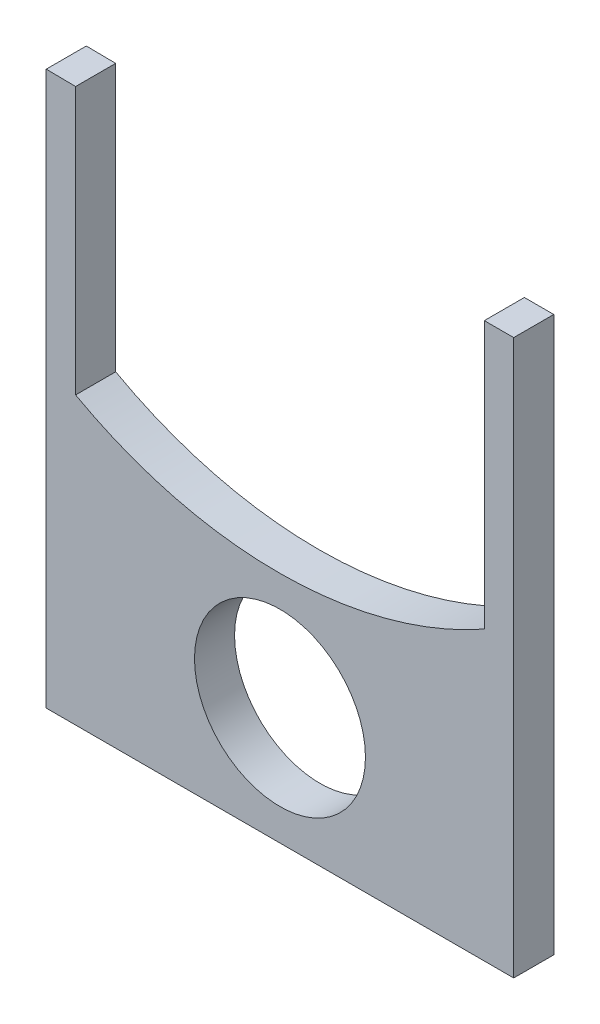
SolidWorks part; units mm, degrees
ref_plane "Front Plane" through (0, 0, 0) normal (0, 0, 1) x (1, 0, 0)
ref_plane "Top Plane" through (0, 0, 0) normal (0, 1, 0) x (1, 0, 0)
ref_plane "Right Plane" through (0, 0, 0) normal (1, 0, 0) x (0, 0, -1)
sketch "Sketch1" plane through (0, 0, 0) normal (0, 0, 1) x (1, 0, 0)
  line L0 (-17.5, 13.936) -> (-15.3001, 13.9108)
  line L1 (17.5, -27.4952) -> (-17.5, -27.4952)
  line L2 (17.5, -27.4952) -> (17.5, 14.0298)
  line L4 (-17.5, -27.4952) -> (-17.5, 13.936)
  line L6 (-15.3001, 13.9108) -> (-15.3001, -6.0892)
  line L8 (15.3, 14.0298) -> (15.3, -5.9702)
  line L9 (15.3, 14.0298) -> (17.5, 14.0298)
  circle A1 centre (0, -18.7309) radius 6.4
  arc A2 (15.3, -5.9702) -> (-15.3001, -6.0892) centre (-0.1067, 21.3886) cw
  point P0 (0, -18.7309)
  point P10 (0, -27.4952)
extrude "Boss-Extrude1" add sketch "Sketch1" along normal blind 3
